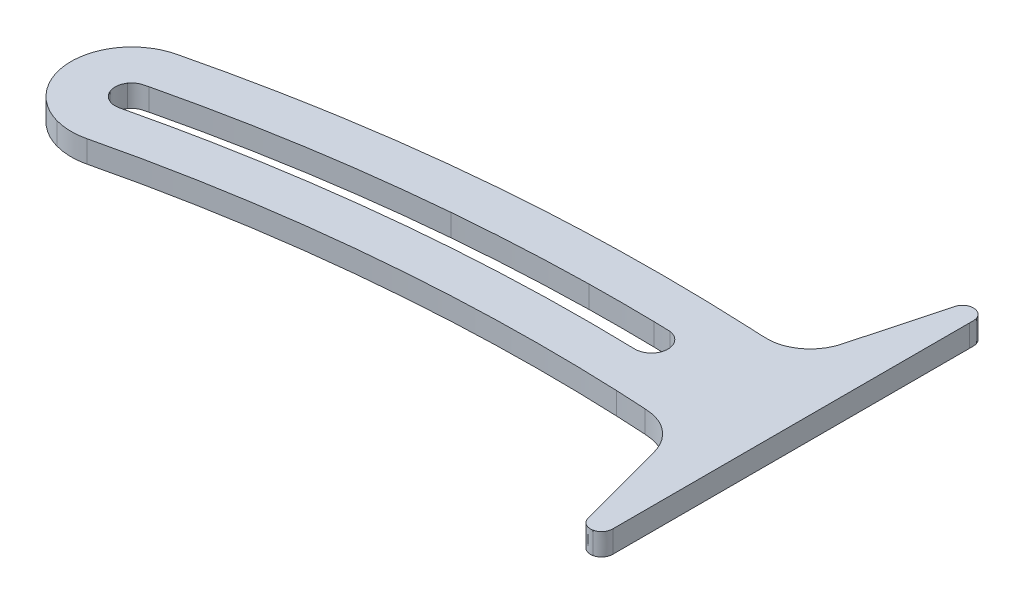
SolidWorks part; units mm, degrees
ref_plane "Front Plane" through (0, 0, 0) normal (0, 0, 1) x (1, 0, 0)
ref_plane "Top Plane" through (0, 0, 0) normal (0, 1, 0) x (1, 0, 0)
ref_plane "Right Plane" through (0, 0, 0) normal (1, 0, 0) x (0, 0, -1)
sketch "Imported Profile" plane through (0, 0, 0) normal (0, 1, 0) x (1, 0, 0)
  spline S0 degree 3 poles (12.8991, 25.236) (15.9171, 24.4093) (18.7007, 24.3473) (21.7531, 25.0501) knots 0 0 0 0 1 1 1 1
  spline S1 degree 3 poles (21.7531, 25.0501) (67.2422, 35.9573) (114.0335, 40.4773) (160.7696, 38.4929) knots 0 0 0 0 1 1 1 1
  spline S2 degree 3 poles (160.7696, 38.4929) (163.6635, 38.3689) (166.5574, 38.2174) (169.4444, 38.0449) knots 0 0 0 0 1 1 1 1
  spline S3 degree 3 poles (169.4444, 38.0449) (172.5863, 37.8589) (175.1081, 37.0734) (177.5541, 34.9719) knots 0 0 0 0 1 1 1 1
  spline S4 degree 3 poles (177.5541, 34.9719) (178.7254, 33.9728) (179.6419, 32.8428) (180.3929, 31.4993) knots 0 0 0 0 1 1 1 1
  spline S5 degree 3 poles (180.3929, 31.4993) (181.1026, 30.2177) (181.4953, 28.8603) (181.8674, 27.4685) knots 0 0 0 0 1 1 1 1
  spline S6 degree 3 poles (181.8674, 27.4685) (182.6184, 24.6642) (183.3694, 21.8599) (184.1205, 19.0625) knots 0 0 0 0 1 1 1 1
  spline S7 degree 3 poles (184.1205, 19.0625) (184.8715, 16.2582) (185.6225, 13.4539) (186.3735, 10.6495) knots 0 0 0 0 1 1 1 1
  spline S8 degree 3 poles (186.3735, 10.6495) (186.7457, 9.2508) (187.1246, 7.8521) (187.4967, 6.4465) knots 0 0 0 0 1 1 1 1
  spline S9 degree 3 poles (187.4967, 6.4465) (187.6827, 5.7506) (187.8756, 5.0478) (188.0617, 4.345) knots 0 0 0 0 1 1 1 1
  spline S10 degree 3 poles (188.0617, 4.345) (188.2477, 3.6491) (188.3786, 2.9463) (188.6335, 2.2642) knots 0 0 0 0 1 1 1 1
  spline S11 degree 3 poles (188.6335, 2.2642) (189.1847, 0.8172) (190.7006, -0.0165) (192.2233, 0.2798) knots 0 0 0 0 1 1 1 1
  spline S12 degree 3 poles (192.2233, 0.2798) (193.7874, 0.5968) (194.7796, 1.9335) (194.7796, 3.4975) knots 0 0 0 0 1 1 1 1
  spline S13 degree 3 poles (194.7796, 3.4975) (194.7796, 6.3983) (194.7796, 9.2991) (194.7796, 12.1998) knots 0 0 0 0 1 1 1 1
  spline S14 degree 3 poles (194.7796, 12.1998) (194.7796, 35.5507) (194.7796, 58.9084) (194.7796, 82.2593) knots 0 0 0 0 1 1 1 1
  spline S15 degree 3 poles (194.7796, 82.2593) (194.7796, 88.0608) (194.7796, 93.8624) (194.7796, 99.6708) knots 0 0 0 0 1 1 1 1
  spline S16 degree 3 poles (194.7796, 99.6708) (194.7796, 101.1178) (194.7796, 102.5716) (194.7796, 104.0185) knots 0 0 0 0 1 1 1 1
  spline S17 degree 3 poles (194.7796, 104.0185) (194.7796, 104.742) (194.7796, 105.4724) (194.7796, 106.1958) knots 0 0 0 0 1 1 1 1
  spline S18 degree 3 poles (194.7796, 106.1958) (194.7796, 106.9193) (194.8485, 107.6152) (194.6072, 108.3387) knots 0 0 0 0 1 1 1 1
  spline S19 degree 3 poles (194.6072, 108.3387) (194.1043, 109.7994) (192.6229, 110.6882) (191.0932, 110.4402) knots 0 0 0 0 1 1 1 1
  spline S20 degree 3 poles (191.0932, 110.4402) (190.2595, 110.3027) (189.6807, 109.9717) (189.1433, 109.3171) knots 0 0 0 0 1 1 1 1
  spline S21 degree 3 poles (189.1433, 109.3171) (188.6541, 108.7176) (188.5094, 108.0424) (188.3234, 107.3327) knots 0 0 0 0 1 1 1 1
  spline S22 degree 3 poles (188.3234, 107.3327) (186.8213, 101.731) (185.3193, 96.1292) (183.8172, 90.5206) knots 0 0 0 0 1 1 1 1
  spline S23 degree 3 poles (183.8172, 90.5206) (183.0662, 87.7232) (182.3909, 84.912) (181.5641, 82.1353) knots 0 0 0 0 1 1 1 1
  spline S24 degree 3 poles (181.5641, 82.1353) (180.7097, 79.2483) (178.8563, 76.7678) (176.3413, 75.121) knots 0 0 0 0 1 1 1 1
  spline S25 degree 3 poles (176.3413, 75.121) (172.2486, 72.4477) (169.1411, 73.0678) (164.7796, 73.2676) knots 0 0 0 0 1 1 1 1
  spline S26 degree 3 poles (164.7796, 73.2676) (145.3906, 74.1909) (126.0843, 74.1289) (106.7022, 73.0126) knots 0 0 0 0 1 1 1 1
  spline S27 degree 3 poles (106.7022, 73.0126) (83.2893, 71.6621) (60.2485, 68.6924) (37.2422, 64.1724) knots 0 0 0 0 1 1 1 1
  spline S28 degree 3 poles (37.2422, 64.1724) (29.3115, 62.6153) (21.4154, 60.9065) (13.5537, 58.9979) knots 0 0 0 0 1 1 1 1
  spline S29 degree 3 poles (13.5537, 58.9979) (13.4434, 58.9679) (13.3332, 58.9429) (13.2298, 58.9154) knots 0 0 0 0 1 1 1 1
  spline S30 degree 3 poles (13.2298, 58.9154) (13.0093, 58.8604) (12.7889, 58.7984) (12.5753, 58.7294) knots 0 0 0 0 1 1 1 1
  spline S31 degree 3 poles (12.5753, 58.7294) (12.1274, 58.5914) (11.6933, 58.4469) (11.2661, 58.2744) knots 0 0 0 0 1 1 1 1
  spline S32 degree 3 poles (11.2661, 58.2744) (10.3773, 57.9229) (9.5298, 57.5027) (8.7099, 57.0135) knots 0 0 0 0 1 1 1 1
  spline S33 degree 3 poles (8.7099, 57.0135) (6.9735, 55.9731) (5.5197, 54.726) (4.2313, 53.1688) knots 0 0 0 0 1 1 1 1
  spline S34 degree 3 poles (4.2313, 53.1688) (1.7439, 50.1716) (0.3383, 46.4302) (0.2281, 42.5373) knots 0 0 0 0 1 1 1 1
  spline S35 degree 3 poles (0.2281, 42.5373) (-0.0062, 34.5515) (5.2166, 27.4271) (12.8991, 25.236) knots 0 0 0 0 1 1 1 1
  spline S36 degree 3 poles (153.0044, 51.4685) (156.4908, 51.3706) (158.8886, 54.9191) (157.5036, 58.1161) knots 0 0 0 0 1 1 1 1
  spline S37 degree 3 poles (157.5036, 58.1161) (156.8353, 59.6595) (155.409, 60.7344) (153.7416, 60.948) knots 0 0 0 0 1 1 1 1
  spline S38 degree 3 poles (153.7416, 60.948) (153.2937, 61.01) (149.5386, 61.072) (149.0907, 61.079) knots 0 0 0 0 1 1 1 1
  spline S39 degree 3 poles (149.0907, 61.079) (142.8482, 61.196) (136.5988, 61.203) (130.3494, 61.094) knots 0 0 0 0 1 1 1 1
  spline S40 degree 3 poles (130.3494, 61.094) (117.7059, 60.8805) (105.1106, 60.212) (92.5154, 59.0889) knots 0 0 0 0 1 1 1 1
  spline S41 degree 3 poles (92.5154, 59.0889) (67.2422, 56.8358) (42.4581, 52.8051) (17.7706, 46.9484) knots 0 0 0 0 1 1 1 1
  spline S42 degree 3 poles (17.7706, 46.9484) (16.1652, 46.5694) (14.7734, 46.2387) (13.7329, 44.6953) knots 0 0 0 0 1 1 1 1
  spline S43 degree 3 poles (13.7329, 44.6953) (12.8234, 43.3517) (12.6649, 41.6499) (13.3057, 40.1547) knots 0 0 0 0 1 1 1 1
  spline S44 degree 3 poles (13.3057, 40.1547) (13.9672, 38.6044) (15.4072, 37.5226) (17.0816, 37.309) knots 0 0 0 0 1 1 1 1
  spline S45 degree 3 poles (17.0816, 37.309) (17.8808, 37.2055) (18.6112, 37.359) (19.3691, 37.5365) knots 0 0 0 0 1 1 1 1
  spline S46 degree 3 poles (19.3691, 37.5365) (20.127, 37.7225) (20.8849, 37.9015) (21.6429, 38.074) knots 0 0 0 0 1 1 1 1
  spline S47 degree 3 poles (21.6429, 38.074) (27.7269, 39.5002) (33.8316, 40.8094) (39.9708, 42.0151) knots 0 0 0 0 1 1 1 1
  spline S48 degree 3 poles (39.9708, 42.0151) (52.38, 44.4405) (64.8375, 46.4111) (77.3914, 47.9269) knots 0 0 0 0 1 1 1 1
  spline S49 degree 3 poles (77.3914, 47.9269) (102.5751, 50.9655) (127.6485, 52.1368) (153.0044, 51.4685) knots 0 0 0 0 1 1 1 1
extrude "Boss-Extrude1" add sketch "Imported Profile" along normal blind 6.35
sketch "Sketch1" plane through (0, 6.35, 0) normal (0, 1, 0) x (1, 0, 0)
  line L0 (191.616, 107.3087) -> (191.616, 3.4975) construction
  line L1 (194.7796, 107.3087) -> (194.7796, 3.4975) construction
  line L2 (188.4524, 107.3087) -> (188.4524, 3.4975) construction
  line L5 (194.7796, 12.1998) -> (194.7796, 82.2593) construction
  line L6 (194.7796, 55.4031) -> (171.9196, 55.4031) construction
  arc A0 (194.7796, 107.3087) -> (188.4524, 107.3087) centre (191.616, 107.3087) ccw construction
  arc A1 (188.4524, 3.4975) -> (194.7796, 3.4975) centre (191.616, 3.4975) ccw construction
  spline S0 degree 3 poles (194.6072, 108.3387) (194.1043, 109.7994) (192.6229, 110.6882) (191.0932, 110.4402) knots 0 0 0 0 1 1 1 1 construction
  spline S1 degree 3 poles (192.2233, 0.2798) (193.7874, 0.5968) (194.7796, 1.9335) (194.7796, 3.4975) knots 0 0 0 0 1 1 1 1 construction
  point P2 (191.616, 55.4031)
  point P15 (191.616, 107.3087)
  point P16 (188.4524, 107.3087)
  point P17 (171.9196, 55.4031)
  dimension "D1" = 22.86
  dimension "D2" = 6.3272
sketch3d "3DSketch1"
  line L0 (171.9196, 6.35, -55.4031) -> (171.9196, 0, -55.4031) construction
